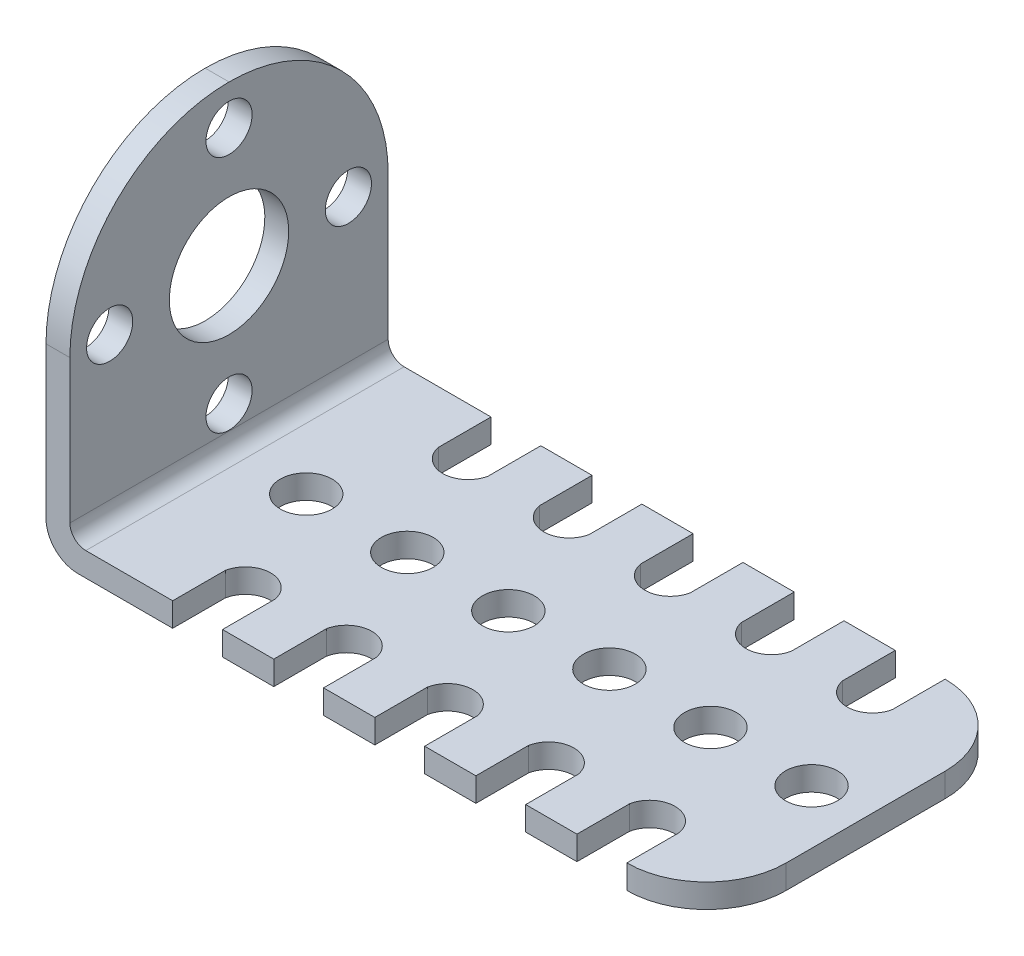
SolidWorks part; units mm, degrees
material "1060 Alloy"
ref_plane "Front Plane" through (0, 0, 0) normal (0, 0, 1) x (1, 0, 0)
ref_plane "Top Plane" through (0, 0, 0) normal (0, 1, 0) x (1, 0, 0)
ref_plane "Right Plane" through (0, 0, 0) normal (1, 0, 0) x (0, 0, -1)
sketch "Sketch1" plane through (0, 0, 0) normal (0, 0, 1) x (1, 0, 0)
  line L0 (0, 0) -> (41.5, 0)
  line L1 (41.5, 0) -> (41.5, 1.5)
  line L2 (1.5, 1.5) -> (41.5, 1.5)
  line L3 (1.5, 1.5) -> (1.5, 21.5)
  line L4 (1.5, 21.5) -> (0, 21.5)
  line L5 (0, 21.5) -> (0, 0)
  dimension "D1" = 40
  dimension "D2" = 1.5
  dimension "D3" = 20
extrude "Boss-Extrude1" add sketch "Sketch1" along normal blind 20
fillet "Fillet1" radius 2 1 edges at (0, 0, 10)
fillet "Fillet2" radius 1 1 edges at (1.5, 1.5, 10)
sketch "Sketch3" plane through (0, 1.5, 0) normal (0, 1, 0) x (1, 0, 0)
  line L0 (41.5, 0) -> (2.5, 0) construction
  line L1 (7.96, 0) -> (11.09, 0)
  line L2 (7.96, 0) -> (7.96, -3.3072)
  line L3 (0, -20) -> (0, 0) construction
  line L4 (11.09, 0) -> (11.09, -3.3072)
  line L5 (14.31, 0) -> (17.44, 0)
  line L6 (14.31, 0) -> (14.31, -3.3072)
  line L7 (17.44, 0) -> (17.44, -3.3072)
  line L8 (20.66, 0) -> (23.79, 0)
  line L9 (20.66, 0) -> (20.66, -3.3072)
  line L10 (23.79, 0) -> (23.79, -3.3072)
  line L11 (27.01, 0) -> (30.14, 0)
  line L12 (27.01, 0) -> (27.01, -3.3072)
  line L13 (30.14, 0) -> (30.14, -3.3072)
  line L14 (33.36, 0) -> (36.49, 0)
  line L15 (33.36, 0) -> (33.36, -3.3072)
  line L16 (36.49, 0) -> (36.49, -3.3072)
  line L17 (0, -10) -> (51.2037, -10) construction
  line L18 (36.49, -20) -> (36.49, -16.6928)
  line L19 (33.36, -20) -> (33.36, -16.6928)
  line L20 (33.36, -20) -> (36.49, -20)
  line L21 (30.14, -20) -> (30.14, -16.6928)
  line L22 (27.01, -20) -> (27.01, -16.6928)
  line L23 (27.01, -20) -> (30.14, -20)
  line L24 (23.79, -20) -> (23.79, -16.6928)
  line L25 (20.66, -20) -> (20.66, -16.6928)
  line L26 (20.66, -20) -> (23.79, -20)
  line L27 (17.44, -20) -> (17.44, -16.6928)
  line L28 (14.31, -20) -> (14.31, -16.6928)
  line L29 (14.31, -20) -> (17.44, -20)
  line L30 (11.09, -20) -> (11.09, -16.6928)
  line L31 (7.96, -20) -> (7.96, -16.6928)
  line L32 (7.96, -20) -> (11.09, -20)
  arc A0 (7.96, -3.3072) -> (11.09, -3.3072) centre (9.525, -3) ccw
  arc A1 (14.31, -3.3072) -> (17.44, -3.3072) centre (15.875, -3) ccw
  arc A2 (20.66, -3.3072) -> (23.79, -3.3072) centre (22.225, -3) ccw
  arc A3 (27.01, -3.3072) -> (30.14, -3.3072) centre (28.575, -3) ccw
  arc A4 (33.36, -3.3072) -> (36.49, -3.3072) centre (34.925, -3) ccw
  arc A5 (33.36, -16.6928) -> (36.49, -16.6928) centre (34.925, -17) cw
  arc A6 (27.01, -16.6928) -> (30.14, -16.6928) centre (28.575, -17) cw
  arc A7 (20.66, -16.6928) -> (23.79, -16.6928) centre (22.225, -17) cw
  arc A8 (14.31, -16.6928) -> (17.44, -16.6928) centre (15.875, -17) cw
  arc A9 (7.96, -16.6928) -> (11.09, -16.6928) centre (9.525, -17) cw
  dimension "D1" = 3.13
  dimension "D2" = 3
  dimension "D3" = 9.525
  dimension "D4" = 5
extrude "Cut-Extrude1" cut sketch "Sketch3" against normal through all
hole_wizard "#4 Clearance Hole1" positions "Sketch6" profile "Sketch4" hole size "#4" standard "ANSI Inch" end condition through all
sketch "Sketch6" plane through (0, 1.5, 0) normal (0, 1, 0) x (1, 0, 0)
  line L0 (0, -20) -> (0, 0) construction
  point P0 (6.35, -10)
  point P2 (12.7, -10)
  point P4 (25.4, -10)
  point P6 (31.75, -10)
  point P8 (38.1, -10)
  point P10 (19.05, -10)
  point P17 (0, -10)
  dimension "D1" = 6.35
  dimension "D2" = 6.35
  dimension "D3" = 6.35
  dimension "D4" = 6.35
  dimension "D5" = 6.35
  dimension "D6" = 6.35
sketch "Sketch4" plane through (6.35, 1.5, 10) normal (1, 0, 0) x (0, 0, 1)
  line L0 (0, 0) -> (0, 1.5)
  line L1 (0, 1.5) -> (1.6319, 1.5)
  line L2 (1.6319, 1.5) -> (1.6319, 0)
  line L5 (1.6319, 0) -> (0, 0)
  line L11 (0, -6.35) -> (0, 107.95) construction
  dimension "Thru Hole Dia." = 3.2639
  dimension "Thru Hole Depth" = 1.5
fillet "Fillet3" radius 5 2 edges at (41.5, 0.75, 20) (41.5, 0.75, 0)
fillet "Fillet4" radius 10 2 edges at (0.75, 21.5, 0) (0.75, 21.5, 20)
sketch "Sketch7" plane through (0, 0, 0) normal (-1, 0, 0) x (0, 0, 1)
  line L0 (20, 0) -> (0, 0) construction
  circle A0 centre (10, 11.5) radius 3.75
  circle A1 centre (10, 19) radius 1.45
  circle A2 centre (17.5, 11.5) radius 1.45
  circle A3 centre (10, 4) radius 1.45
  circle A4 centre (2.5, 11.5) radius 1.45
  dimension "D1" = 2.9
  dimension "D2" = 7.5
  dimension "D3" = 11.5
  dimension "D4" = 15
  dimension "D5" = 15
  dimension "D6" = 7.5
  dimension "D7" = 7.5
extrude "Cut-Extrude2" cut sketch "Sketch7" against normal through all
ref_plane "Plane1" through (0, 0, 10) normal (0, 0, 1) x (1, 0, 0)
equation "\"D2@Sketch6\"=\"D1@Sketch6\""
equation "\"D3@Sketch6\"=\"D1@Sketch6\""
equation "\"D4@Sketch6\"=\"D1@Sketch6\""
equation "\"D5@Sketch6\"=\"D1@Sketch6\""
